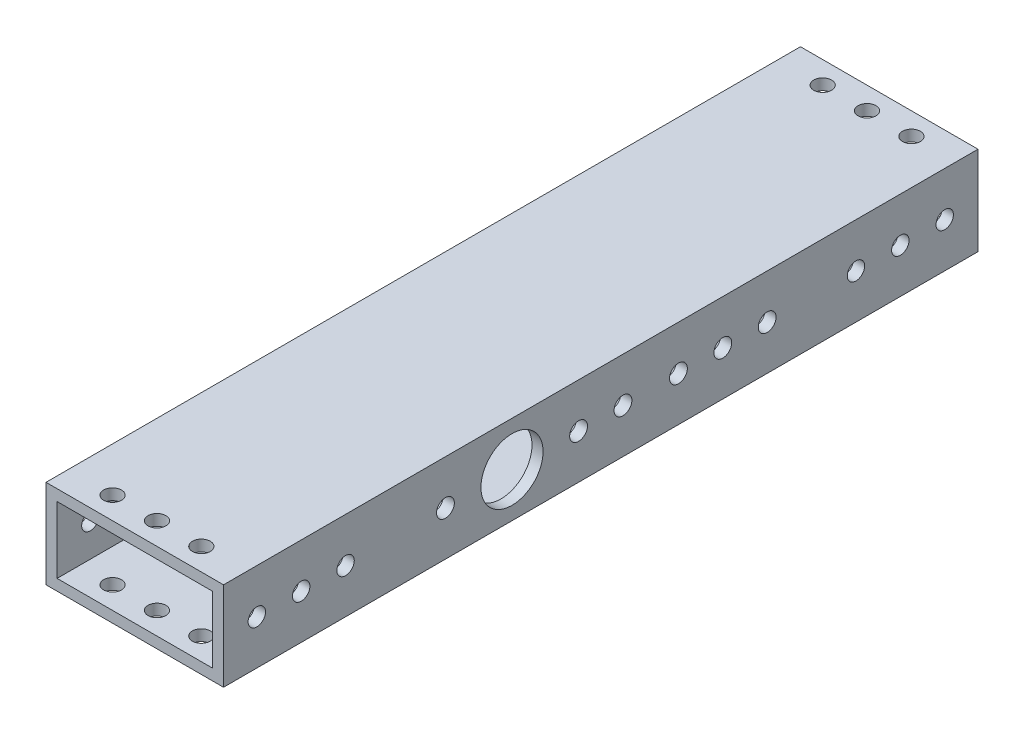
SolidWorks part; units mm, degrees
material "6061-T6 (SS)"
ref_plane "Front Plane" through (0, 0, 0) normal (0, 0, 1) x (1, 0, 0)
ref_plane "Top Plane" through (0, 0, 0) normal (0, 1, 0) x (1, 0, 0)
ref_plane "Right Plane" through (0, 0, 0) normal (1, 0, 0) x (0, 0, -1)
sketch "Sketch1" plane through (0, 0, 0) normal (0, 0, 1) x (1, 0, 0)
  line L0 (-22.225, 9.525) -> (22.225, 9.525)
  line L1 (-25.4, -12.7) -> (25.4, -12.7)
  line L2 (-25.4, -12.7) -> (-25.4, 12.7)
  line L3 (-25.4, 12.7) -> (25.4, 12.7)
  line L4 (25.4, -12.7) -> (25.4, 12.7)
  line L5 (-25.4, -12.7) -> (25.4, 12.7) construction
  line L6 (-25.4, 12.7) -> (25.4, -12.7) construction
  line L7 (22.225, -9.525) -> (22.225, 9.525)
  line L8 (-22.225, -9.525) -> (22.225, -9.525)
  line L9 (-22.225, -9.525) -> (-22.225, 9.525)
  point P0 (0, 0)
  dimension "D1" = 50.8
  dimension "D2" = 25.4
  dimension "D3" = 3.175
extrude "Boss-Extrude1" add sketch "Sketch1" along normal mid plane 215.9
sketch "Sketch3" plane through (0, 12.7, 0) normal (0, 1, 0) x (1, 0, 0)
  line L0 (-25.4, 0) -> (25.4, 0) construction
  line L1 (-25.4, -107.95) -> (-25.4, 107.95) construction
  line L2 (25.4, -107.95) -> (25.4, 107.95) construction
  line L3 (25.4, -107.95) -> (-25.4, -107.95) construction
  circle A0 centre (-12.7, -101.6) radius 2.5527
  circle A1 centre (0, -101.6) radius 2.5527
  circle A2 centre (12.7, -101.6) radius 2.5527
  circle A3 centre (12.7, 101.6) radius 2.5527
  circle A4 centre (0, 101.6) radius 2.5527
  circle A5 centre (-12.7, 101.6) radius 2.5527
  dimension "D1" = 5.1054
  dimension "D2" = 12.7
  dimension "D3" = 12.7
  dimension "D4" = 6.35
extrude "Cut-Extrude2" cut sketch "Sketch3" against normal through all
sketch "Sketch4" plane through (25.4, 0, 0) normal (1, 0, 0) x (0, 0, -1)
  line L0 (-25.4, 0) -> (-45.1908, 0) construction
  line L1 (-16.51, 0) -> (-34.29, 0) construction
  line L8 (-25.4, 0) -> (34.925, 0) construction
  line L9 (0, 12.7) -> (0, -12.7) construction
  line L10 (-107.95, 12.7) -> (107.95, 12.7) construction
  line L11 (-107.95, -12.7) -> (107.95, -12.7) construction
  circle A0 centre (-25.4, 0) radius 8.89
  circle A9 centre (34.925, 0) radius 2.5527
  circle A10 centre (22.225, 0) radius 2.5527
  dimension "D2" = 17.78
  dimension "D3" = 25.4
  dimension "D1" = 60.325
  dimension "D4" = 5.1054
  dimension "D6" = 47.625
extrude "Cut-Extrude3" cut sketch "Sketch4" against normal through all contours A0 | A9 | A10
sketch "Sketch2" plane through (25.4, 0, 0) normal (1, 0, 0) x (0, 0, -1)
  line L0 (-107.95, -12.7) -> (-107.95, 12.7) construction
  line L1 (0, 12.7) -> (0, -12.7) construction
  line L2 (-107.95, 12.7) -> (107.95, 12.7) construction
  line L3 (-107.95, -12.7) -> (107.95, -12.7) construction
  circle A0 centre (-98.425, 0) radius 2.4892
  circle A1 centre (98.425, 0) radius 2.4892
  circle A2 centre (-85.725, 0) radius 2.4892
  circle A3 centre (-73.025, 0) radius 2.4892
  circle A4 centre (73.025, 0) radius 2.4892
  circle A5 centre (85.725, 0) radius 2.4892
  dimension "D2" = 4.9784
  dimension "D5" = 4.9784
  dimension "D1" = 9.525
  dimension "D3" = 12.7
  dimension "D4" = 12.7
extrude "Cut-Extrude1" cut sketch "Sketch2" against normal through all
sketch "Sketch5" plane through (0, -12.7, 0) normal (0, -1, 0) x (1, 0, 0)
  line L0 (-25.4, 107.95) -> (-25.4, -107.95) construction
  line L1 (-25.4, 107.95) -> (25.4, 107.95) construction
  line L4 (25.4, 25.4) -> (-25.4, 25.4) construction
  line L5 (25.4, 107.95) -> (25.4, -107.95) construction
  circle A0 centre (-3.81, 69.85) radius 2.4892
  circle A1 centre (-16.51, 69.85) radius 2.4892
  circle A2 centre (-16.51, 57.15) radius 2.4892
  circle A3 centre (-3.81, 57.15) radius 2.4892
  circle A8 centre (-3.81, -6.35) radius 2.4892
  circle A9 centre (-16.51, -6.35) radius 2.4892
  circle A10 centre (-16.51, -19.05) radius 2.4892
  circle A11 centre (-3.81, -19.05) radius 2.4892
  dimension "D3" = 4.9784
  dimension "D4" = 8.89
  dimension "D7" = 12.7
  dimension "D12" = 82.55
  dimension "D5" = 31.75
  dimension "D6" = 12.7
  dimension "D1" = 2
  dimension "D2" = 2
extrude "Cut-Extrude4" cut sketch "Sketch5" against normal up to next
sketch "Sketch7" plane through (25.4, 0, 0) normal (1, 0, 0) x (0, 0, -1)
  circle A0 centre (47.625, 0) radius 2.5527
  circle A1 centre (34.925, 0) radius 2.5527 construction
  circle A5 centre (6.35, 0) radius 2.5527
  circle A6 centre (-6.35, 0) radius 2.5527
  circle A7 centre (-44.45, 0) radius 2.5527
  circle A8 centre (-25.4, 0) radius 8.89 construction
  point P15 (0, 0)
  dimension "D1" = 12.7
  dimension "D2" = 19.05
  dimension "D3" = 19.05
  dimension "D4" = 12.7
extrude "Cut-Extrude5" cut sketch "Sketch7" against normal up to next contours A0 | A7 | A6 | A5
